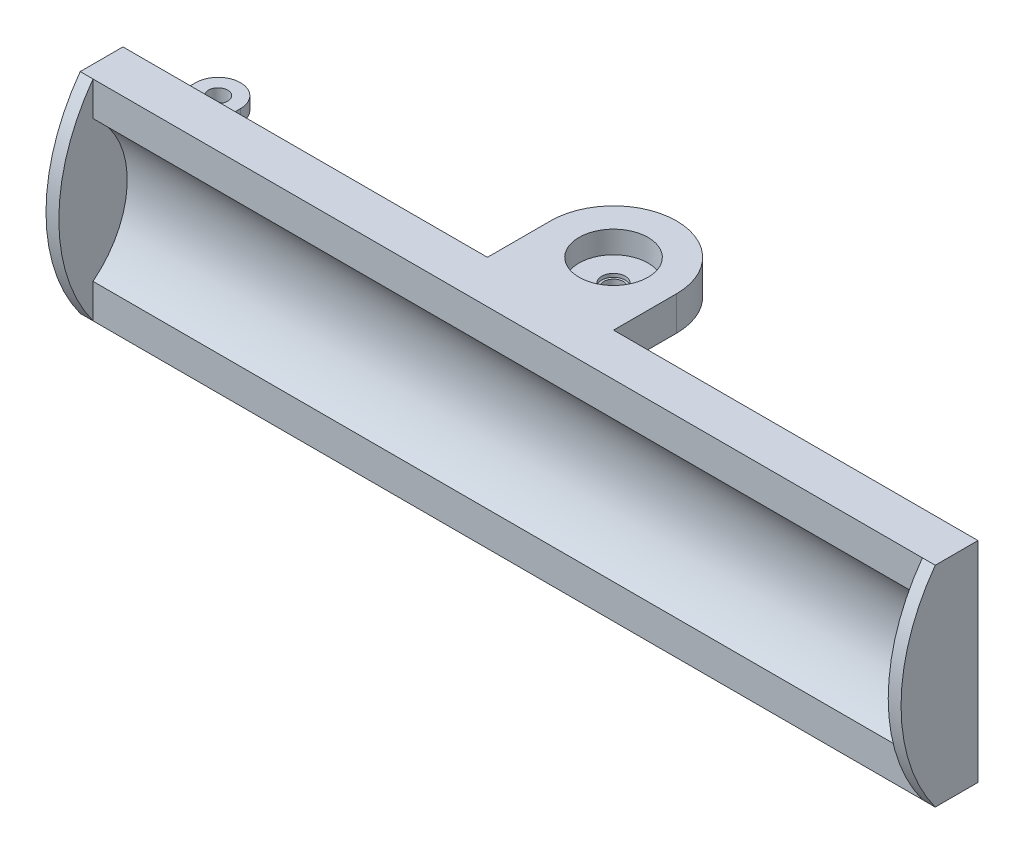
SolidWorks part; units mm, degrees
ref_plane "Front Plane" through (0, 0, 0) normal (1, 0, 0) x (0, 1, 0)
ref_plane "Top Plane" through (0, 0, 0) normal (0, 0, 1) x (0, 1, 0)
ref_plane "Right Plane" through (0, 0, 0) normal (0, 1, 0) x (-1, 0, 0)
sketch "Sketch1" plane through (0, 0, 0) normal (1, 0, 0) x (0, 1, 0)
  line L0 (-5.9881, -2) -> (7.7891, -2) construction
  line L1 (-24.5, -5) -> (24.5, -5)
  line L2 (-24.5, -5) -> (-24.5, 5)
  line L3 (-24.5, 5) -> (24.5, 5)
  line L4 (24.5, -5) -> (24.5, 5)
  line L5 (-24.5, -5) -> (24.5, 5) construction
  line L6 (-24.5, 5) -> (24.5, -5) construction
  circle A0 centre (0, 18) radius 20 construction
  circle A1 centre (0, 18) radius 21
  point P0 (0, 0)
  dimension "D3" = 40
  dimension "D4" = 3
  dimension "D1" = 49
  dimension "D2" = 10
  dimension "D5" = 1
extrude "Boss-Extrude1" add sketch "Sketch1" along normal mid plane 200 contours A1 L3 L2 L1 L4 region at (0, -23.9999, 0)
ref_plane "Midplane Width" through (0, 0, 0) normal (0, -1, 0) x (-1, 0, 0)
sketch "Sketch3" plane through (0, -24.5, 0) normal (0, -1, 0) x (1, 0, 0)
  line L0 (100, -5) -> (-100, -5) construction
  line L1 (-14.75, -19.75) -> (-14.75, -5)
  line L2 (14.75, -19.75) -> (14.75, -5)
  line L3 (-14.75, -5) -> (14.75, -5)
  circle A0 centre (0, -19.75) radius 2.75
  circle A1 centre (0, -19.75) radius 14.75
  line M4 (-100, -5) -> (100, -5)
  dimension "D1" = 5.5
  dimension "D2" = 12
extrude "Boss-Extrude2" add sketch "Sketch3" against normal blind 8 contours A1 A0 | A1 L1 M4 | A1 L2 L3 region at (-10.1348, -24.5, -9.6152) region at (-11.4553, -24.5, -8.2947) region at (11.4553, -24.5, -8.2947)
sketch "Sketch4" plane through (0, -24.5, 0) normal (0, -1, 0) x (-1, 0, 0)
  circle A0 centre (0, 19.75) radius 8.075
  circle A1 centre (0, 19.75) radius 2.75 construction
  circle A2 centre (0, 19.75) radius 2.75
  dimension "D1" = 16.15
extrude "Cut-Extrude1" cut sketch "Sketch4" against normal blind 5.2
sketch "Sketch5" plane through (0, -16.5, 0) normal (0, 1, 0) x (-1, 0, 0)
  circle A0 centre (0, -19.75) radius 2.25
  circle A1 centre (0, -19.75) radius 2.75 construction
  circle A2 centre (0, -19.75) radius 2.75
  dimension "D1" = 4.5
extrude "Boss-Extrude4" add sketch "Sketch5" against normal blind 2
mirror "Mirror1" about plane through (0, 0, 0) normal (0, -1, 0) of "Boss-Extrude4", "Boss-Extrude2", "Cut-Extrude1"
sketch "Sketch6" plane through (0, 0, 0) normal (0, -1, 0) x (-1, 0, 0)
  line L0 (0, 19.75) -> (92.5, 19.75)
  line L1 (87.25, 19.75) -> (87.25, 5)
  line L2 (14.75, 5) -> (100, 5) construction
  line L3 (97.75, 19.75) -> (97.75, 5)
  line L4 (97.75, 5) -> (87.25, 5)
  circle A0 centre (92.5, 19.75) radius 2.25
  arc A1 (97.75, 19.75) -> (87.25, 19.75) centre (92.5, 19.75) ccw
  circle A2 centre (92.5, 19.75) radius 5.25 construction
  dimension "D2" = 4.5
  dimension "D1" = 92.5
  dimension "D3" = 3
extrude "Boss-Extrude5" add sketch "Sketch6" along normal blind 3 from offset 8 contours L3 A1 A0 L1 L4 region at (-92.5, 0, -14.0126)
mirror "Mirror2" about plane through (0, 0, 0) normal (0, -1, 0) of "Boss-Extrude5"
sketch "Sketch7" plane through (-100, 0, 0) normal (-1, 0, 0) x (0, -1, 0)
  line L0 (0, 13) -> (-33.9955, 13) construction
  line L1 (-16.4924, 5) -> (16.4924, 5)
  line L5 (-16.4924, 5) -> (-24.5, 5)
  line L6 (-24.5, 5) -> (-24.5, -5)
  line L7 (-24.5, -5) -> (24.5, -5)
  line L8 (24.5, -5) -> (24.5, 5)
  line L9 (24.5, 5) -> (16.4924, 5)
  line L10 (-16.4924, 5) -> (-24.5, 5)
  line L11 (-24.5, 5) -> (-24.5, -5)
  line L12 (-24.5, -5) -> (24.5, -5)
  line L13 (24.5, -5) -> (24.5, 5)
  line L14 (24.5, 5) -> (16.4924, 5)
  arc A0 (24.5, 5) -> (-24.5, 5) centre (0, -28.5156) ccw
  arc A1 (-16.4924, 5) -> (16.4924, 5) centre (0, 18) ccw
  arc A2 (-16.4924, 5) -> (16.4924, 5) centre (0, 18) ccw
  arc M9 (16.4924, 5) -> (-16.4924, 5) centre (0, 18) cw
  line M10 (-16.4924, 5) -> (-24.5, 5)
  line M11 (-24.5, 5) -> (-24.5, -5)
  line M12 (-24.5, -5) -> (24.5, -5)
  line M13 (24.5, -5) -> (24.5, 5)
  line M14 (24.5, 5) -> (16.4924, 5)
  dimension "D2" = 8
  dimension "D1" = 0
extrude "Boss-Extrude6" add sketch "Sketch7" against normal blind 3 contours M14 M9 M10 M11 M12 M13 | L1 M9 | A0 L1 M14 M10 region at (-100, 0, 8.228) region at (-100, 0, -3.5001) region at (-100, 0, 1.7412)
mirror "Mirror3" about plane through (0, 0, 0) normal (1, 0, 0) of "Boss-Extrude6"
